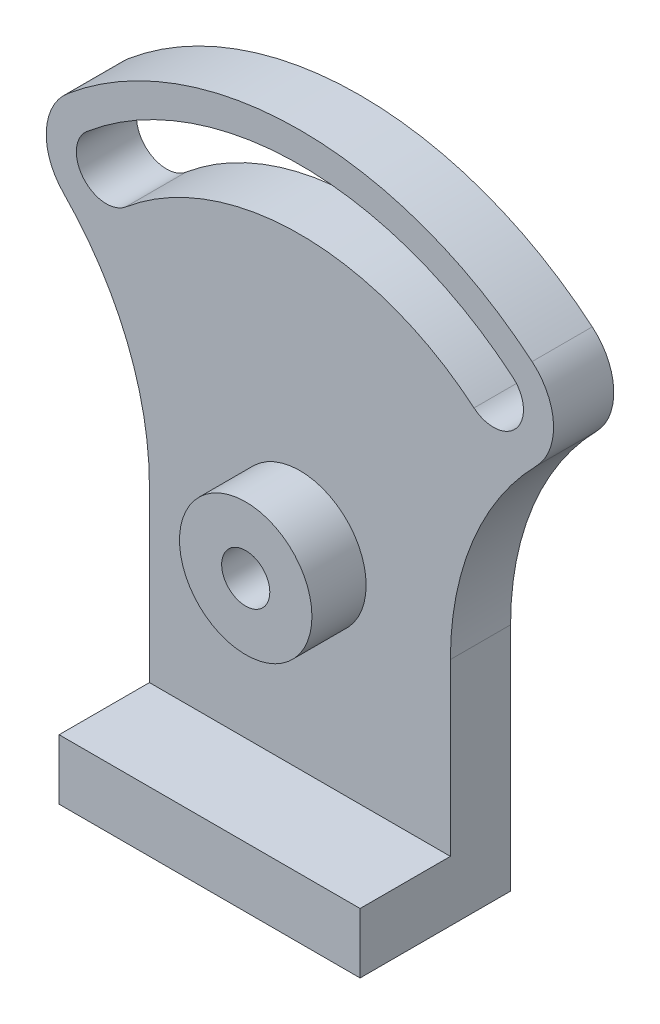
SolidWorks part; units mm, degrees
ref_plane "Front Plane" through (0, 0, 0) normal (0, 0, 1) x (1, 0, 0)
ref_plane "Top Plane" through (0, 0, 0) normal (0, 1, 0) x (1, 0, 0)
ref_plane "Right Plane" through (0, 0, 0) normal (1, 0, 0) x (0, 0, -1)
sketch "Sketch1" plane through (0, 0, 0) normal (0, 0, 1) x (1, 0, 0)
  line L0 (0.3927, 0) -> (-25591.9893, 0) construction
  line L1 (0, 0) -> (0, -25592.382) construction
  line L2 (-25, -32) -> (25, -32)
  line L3 (-25, -42) -> (25, -42)
  line L4 (25, -42) -> (25, -3.6855)
  line L5 (-25, -42) -> (-25, -3.6855)
  circle A0 centre (0, 0) radius 4
  circle A1 centre (0, 0) radius 11
  arc A2 (-32.1394, 38.3022) -> (32.1394, 38.3022) centre (0, 0) cw construction
  arc A3 (35.3533, 42.1324) -> (-35.3533, 42.1324) centre (0, 0) ccw
  arc A4 (28.9254, 34.472) -> (-28.9254, 34.472) centre (0, 0) ccw
  arc A5 (28.9254, 34.472) -> (35.3533, 42.1324) centre (32.1394, 38.3022) ccw
  arc A6 (-35.3533, 42.1324) -> (-28.9254, 34.472) centre (-32.1394, 38.3022) ccw
  arc A7 (32.1394, 38.3022) -> (-32.1394, 38.3022) centre (0, 0) ccw construction
  arc A8 (38.5673, 45.9627) -> (-38.5673, 45.9627) centre (0, 0) ccw
  arc A9 (25.7115, 30.6418) -> (-25.7115, 30.6418) centre (0, 0) ccw
  arc A10 (25.7115, 30.6418) -> (38.5673, 45.9627) centre (32.1394, 38.3022) ccw
  arc A11 (-38.5673, 45.9627) -> (-25.7115, 30.6418) centre (-32.1394, 38.3022) ccw
  arc A12 (-25, -3.6855) -> (-39.2828, 31.3043) centre (-75, -3.6855) ccw
  arc A13 (25, -3.6855) -> (39.2828, 31.3043) centre (75, -3.6855) cw
  point P10 (0, 50)
  point P15 (0, 50)
  point P26 (0, -52)
  point P29 (0, -42)
  point P30 (0, -32)
  dimension "D1" = 22
  dimension "D2" = 8
  dimension "D3" = 10
  dimension "D5" = 50
  dimension "D6" = 20
  dimension "D8" = 50
  dimension "D12" = 50
  dimension "D9" = 42
  dimension "D10" = 10
  dimension "D11" = 50
  dimension "D4" = 80
  dimension "D7" = 80
extrude "Boss-Extrude1" add sketch "Sketch1" along normal blind 10 contours A13 A10 A9 A11 A12 L5 L2 L4 A1 | A8 A11 A9 A10 A6 A3 A5 A4 region at (-23.9343, -17.8427, 0) region at (0, 44.0847, 0)
extrude "Boss-Extrude2" add sketch "Sketch1<3>" along normal blind 25 contours L5 L3 L4 L2 region at (0, -37, 0)
sketch "Sketch1<3>" plane through (0, 0, 0) normal (0, 0, 1) x (1, 0, 0) same geometry as "Sketch1"
extrude "Boss-Extrude3" add sketch "Sketch1<4>" along normal blind 19 contours A1 A0 region at (-10.6889, 0, 0)
sketch "Sketch1<4>" plane through (0, 0, 0) normal (0, 0, 1) x (1, 0, 0) same geometry as "Sketch1"
